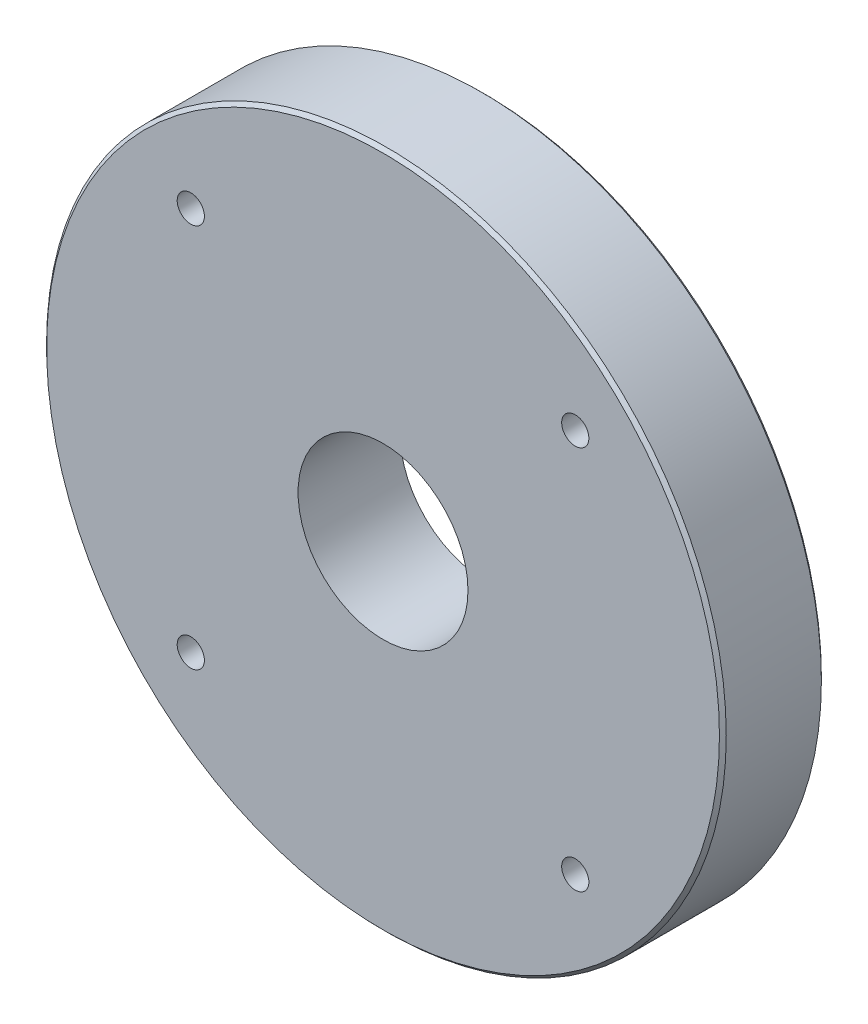
SolidWorks part; units mm, degrees
ref_plane "前视基准面" through (0, 0, 0) normal (0, 0, 1) x (1, 0, 0)
ref_plane "上视基准面" through (0, 0, 0) normal (0, 1, 0) x (1, 0, 0)
ref_plane "右视基准面" through (0, 0, 0) normal (1, 0, 0) x (0, 0, -1)
other "Configuration Table"
sketch "Sketch1" plane through (0, 0, 0) normal (0, 0, 1) x (1, 0, 0)
  circle A0 centre (0, 0) radius 100
extrude "Boss-Extrude1" add sketch "Sketch1" along normal blind 30
sketch "Sketch2" plane through (0, 0, 0) normal (0, 0, 1) x (1, 0, 0)
  circle A0 centre (0, 0) radius 25
extrude "Cut-Extrude2" cut sketch "Sketch2" along normal blind 40
ref_plane "Plane1" through (0, 0, 30) normal (0, 0, 1) x (1, 0, 0)
sketch "Sketch3" plane through (0, 0, 30) normal (0, 0, 1) x (1, 0, 0)
  circle A0 centre (56.5685, 56.5685) radius 4
  circle A1 centre (-56.5685, 56.5685) radius 4
  circle A2 centre (-56.5685, -56.5685) radius 4
  circle A3 centre (56.5685, -56.5685) radius 4
extrude "Cut-Extrude3" cut sketch "Sketch3" against normal blind 40
chamfer "Chamfer1" distance 1 angle 45 1 edges at (100, 0, 0)
chamfer "Chamfer2" distance 1 angle 45 1 edges at (100, 0, 30)
sketch3d "3DSketch1"
  line L0 (0, 0, 0) -> (0, 0, 1000) construction
ref_axis "center_axis_z" through (0, 0, 0) along (0, 0, 1)
ref_plane "bottom_face" through (0, 0, 0) normal (0, 0, 1) x (1, 0, 0)
ref_plane "top_face" through (0, 0, 30) normal (0, 0, 1) x (1, 0, 0)
